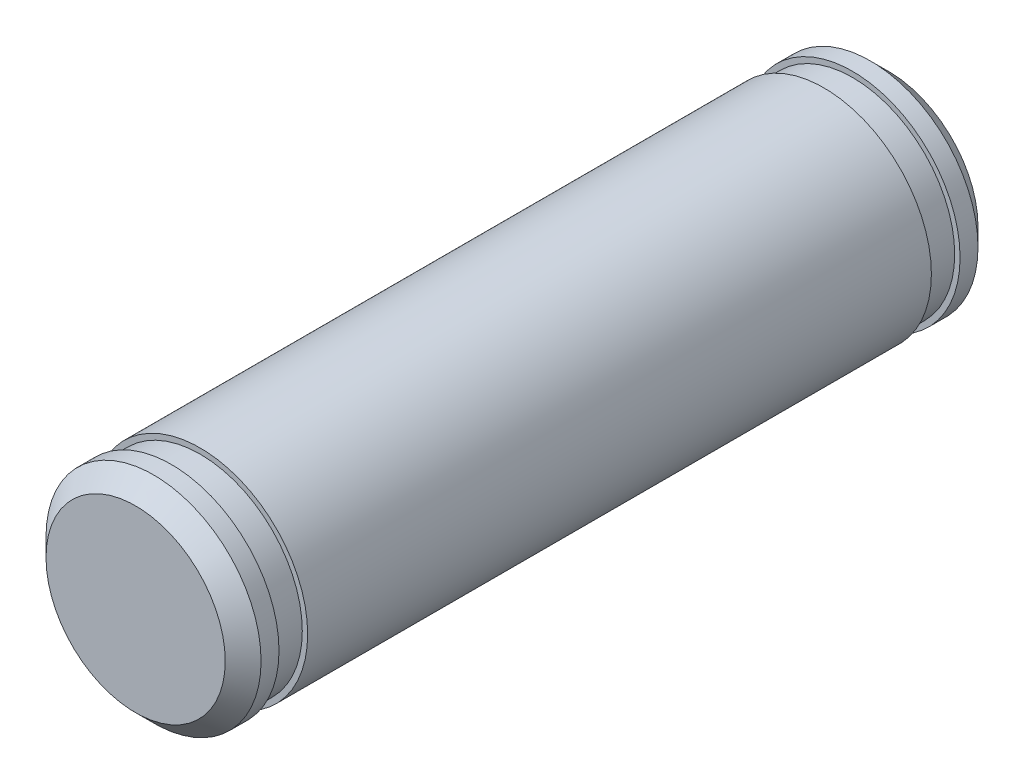
SolidWorks part; units mm, degrees
material "Stop 1060"
ref_plane "Płaszczyzna przednia" through (0, 0, 0) normal (0, 0, 1) x (1, 0, 0)
ref_plane "Płaszczyzna górna" through (0, 0, 0) normal (0, 1, 0) x (1, 0, 0)
ref_plane "Płaszczyzna prawa" through (0, 0, 0) normal (1, 0, 0) x (0, 0, -1)
sketch "Szkic1" plane through (0, 0, 0) normal (0, 0, 1) x (1, 0, 0)
  circle A0 centre (0, 0) radius 3
  dimension "D1" = 6
extrude "Dodanie-wyciągnięcie1" add sketch "Szkic1" along normal blind 21
chamfer "Sfazowanie1" distance 0.5 angle 45 2 edges at (3, 0, 0) (3, 0, 21)
sketch "Szkic2" plane through (0, 0, 21) normal (0, 0, 1) x (1, 0, 0)
  circle A0 centre (0, 0) radius 3
  circle A1 centre (0, 0) radius 2.85
  dimension "D1" = 6
  dimension "D2" = 5.7
extrude "Wytnij-wyciągnięcie1" cut sketch "Szkic2" against normal blind 0.8 from offset 1 offset against normal yes
sketch "Szkic3" plane through (0, 0, 0) normal (0, 0, -1) x (-1, 0, 0)
  circle A0 centre (0, 0) radius 3
  circle A1 centre (0, 0) radius 2.85
  dimension "D1" = 6
  dimension "5,6" = 5.7
extrude "Wytnij-wyciągnięcie2" cut sketch "Szkic3" against normal blind 0.8 from offset 1 offset against normal yes
